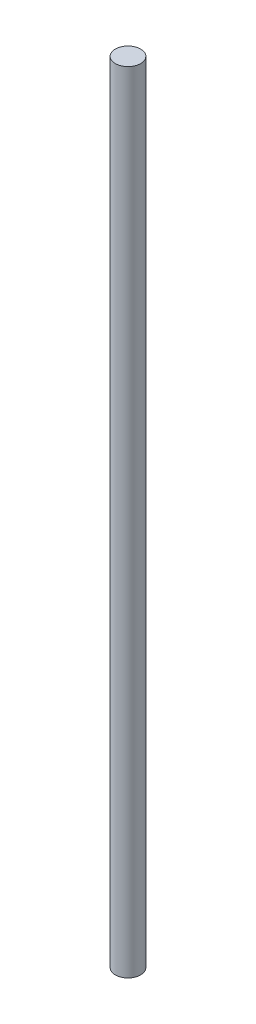
SolidWorks part; units mm, degrees
ref_plane "Front Plane" through (0, 0, 0) normal (0, 0, 1) x (1, 0, 0)
ref_plane "Top Plane" through (0, 0, 0) normal (0, 1, 0) x (1, 0, 0)
ref_plane "Right Plane" through (0, 0, 0) normal (1, 0, 0) x (0, 0, -1)
sketch "Sketch1" plane through (0, 0, 0) normal (0, 1, 0) x (1, 0, 0)
  circle A0 centre (0, 0) radius 4
extrude "Boss-Extrude1" add sketch "Sketch1" along normal blind 250
ref_axis "Axis1" through (0, 250, 0) along (0, -1, 0)
